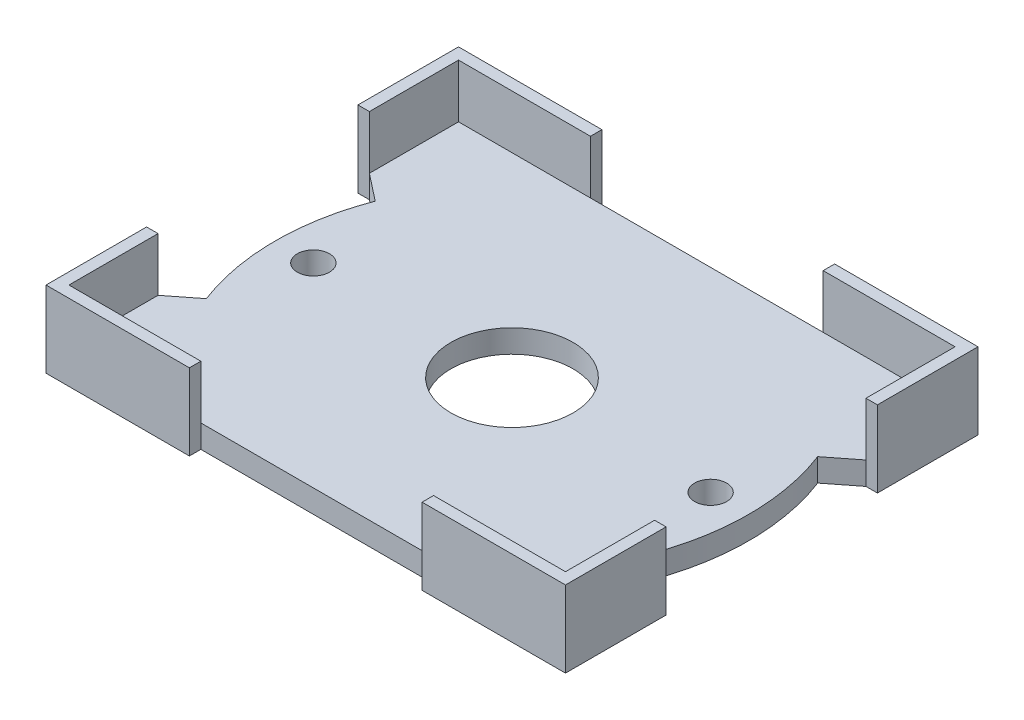
SolidWorks part; units mm, degrees
ref_plane "Front Plane" through (0, 0, 0) normal (0, 0, 1) x (1, 0, 0)
ref_plane "Top Plane" through (0, 0, 0) normal (0, 1, 0) x (1, 0, 0)
ref_plane "Right Plane" through (0, 0, 0) normal (1, 0, 0) x (0, 0, -1)
sketch "Sketch1" plane through (0, 0, 0) normal (0, 1, 0) x (1, 0, 0)
  line L0 (-32.5, 25.5) -> (32.5, -25.5) construction
  line L1 (32.5, -25.5) -> (-32.5, -25.5)
  line L2 (32.5, -25.5) -> (32.5, 25.5)
  line L3 (32.5, 25.5) -> (-32.5, 25.5)
  line L4 (-32.5, -25.5) -> (-32.5, 25.5)
  line L5 (0, 25.5) -> (0, -25.5) construction
  line L6 (32.5, 0) -> (-32.5, 0) construction
  line L7 (-32.5, -25.5) -> (32.5, 25.5) construction
  line L8 (-17.6281, 25.5) -> (-10.4943, 19.9027)
  line L9 (-28.9618, 11.0551) -> (-21.828, 5.4579)
  line L10 (-32.5, -25.5) -> (-17.7016, -13.889)
  line L11 (17.6281, 25.5) -> (10.4943, 19.9027)
  line L12 (-10.4943, -19.9027) -> (-17.6281, -25.5)
  line L13 (-28.9618, 11.0551) -> (-32.5, 13.8313)
  line L14 (-21.828, -5.4579) -> (-32.5, -13.8313)
  line L15 (28.9618, 11.0551) -> (21.828, 5.4579)
  line L16 (21.828, -5.4579) -> (32.5, -13.8313)
  line L17 (10.4943, -19.9027) -> (17.6281, -25.5)
  line L18 (28.9618, 11.0551) -> (32.5, 13.8313)
  line L19 (15.2315, 27) -> (15.2315, 25.5)
  line L20 (34, -27) -> (-34, -27)
  line L21 (34, -27) -> (34, 27)
  line L22 (34, 27) -> (-34, 27)
  line L23 (-34, -27) -> (-34, 27)
  line L24 (0, 27) -> (0, -27) construction
  line L25 (34, 0) -> (-34, 0) construction
  line L26 (15.2315, 25.5) -> (32.5, 25.5)
  line L27 (32.5, 13.8313) -> (34, 13.8313)
  line L28 (34, 13.8313) -> (34, 27)
  line L29 (-32.5, 13.8313) -> (-34, 13.8313)
  line L30 (-15.2315, 27) -> (-15.2315, 25.5)
  line L31 (32.5, -13.8313) -> (34, -13.8313)
  line L32 (15.2315, -27) -> (15.2315, -25.5)
  line L33 (-15.2315, -27) -> (-15.2315, -25.5)
  line L34 (-32.5, -13.8313) -> (-34, -13.8313)
  circle A0 centre (0, 0) radius 22.5
  arc A1 (-17.6281, 25.5) -> (-17.6281, -25.5) centre (0, 0) ccw
  circle A2 centre (-26, 0) radius 2.1
  circle A3 centre (26, 0) radius 2.1
  arc A4 (17.6281, -25.5) -> (17.6281, 25.5) centre (0, 0) ccw
  circle A5 centre (0, 0) radius 8
  point P33 (15.2315, 27)
  dimension "D1" = 45
  dimension "D2" = 62
  dimension "D5" = 4.2
  dimension "D9" = 16
  dimension "D3" = 65
  dimension "D4" = 51
  dimension "D6" = 26
  dimension "D7" = 68
  dimension "D8" = 54
extrude "Boss-Extrude1" add sketch "Sketch1" along normal blind 10 contours L4 L34 L23 L20 L33 L1 | L32 L20 L21 L31 L2 L1 | L2 L27 L21 L22 L19 L3 | L30 L22 L23 L29 L4 L3 region at (32.7293, 0, 19.6656) region at (32.7293, 0, -19.6656) region at (-15.4608, 0, 26.25) region at (-16.4298, 0, -25.7293)
extrude "Boss-Extrude2" add sketch "Sketch1<9>" along normal blind 3 contours A1 L3 L4 L13 | L8 A1 L9 A0 | A0 L11 L3 L8 | L15 A4 L11 A0 | A4 L18 L2 L3 | L16 A4 L15 A0 A3 | L14 A1 L10 A0 | L9 A1 L14 A0 A2 | A1 L14 L4 L10 | A1 L10 L1 | L10 A1 L12 A0 | A0 L12 L1 L17 | L17 A4 L16 A0 | A4 L1 L2 L16 | A0 A5 region at (27.6908, 0, 20.2794) region at (0, 0, 23.5452) region at (20.605, 0, 16.167) region at (0, 0, 21.8636) region at (25.5426, 0, 8.0682) region at (27.6908, 0, -20.2794) region at (-17.7413, 0, 19.8167) region at (20.605, 0, -16.167) region at (-25.0182, 0, 23.4246) region at (-23.4686, 0, 12.5173) region at (0, 0, -23.5452) region at (-29.525, 0, 18.1209) region at (-25.5426, 0, 8.0682) region at (-20.605, 0, -16.167) region at (-27.6908, 0, -20.2794)
sketch "Sketch1<9>" plane through (0, 0, 0) normal (0, 1, 0) x (1, 0, 0) same geometry as "Sketch1"
